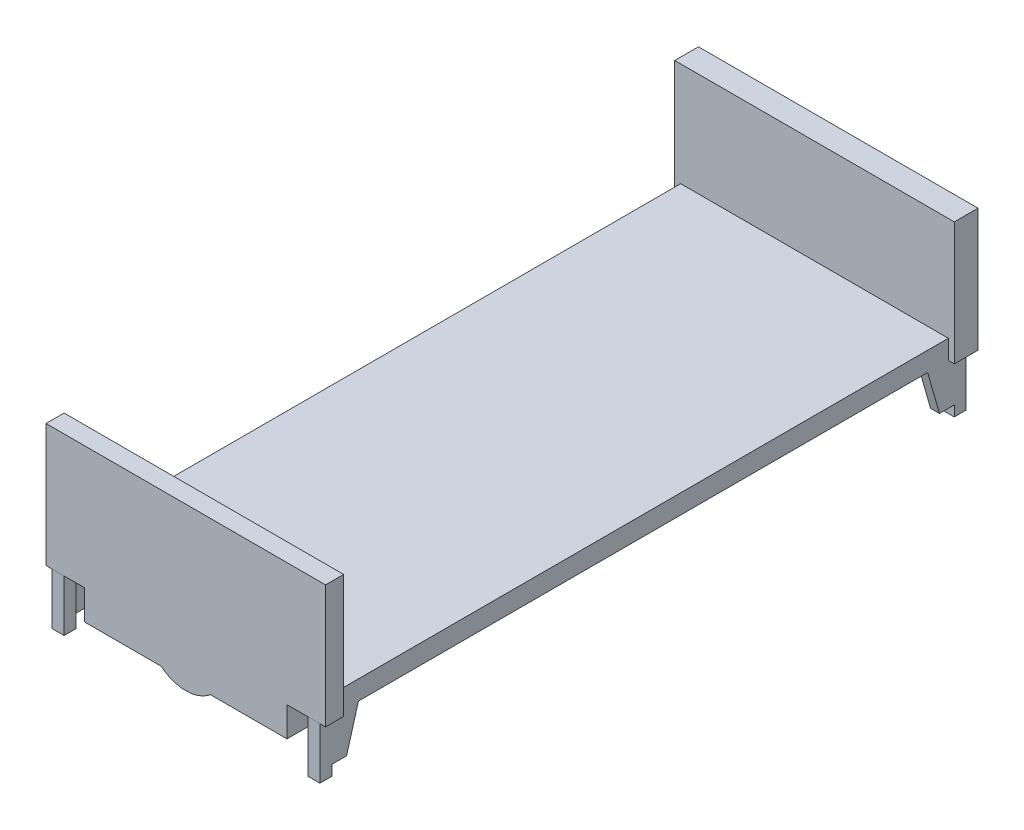
SolidWorks part; units mm, degrees
note: The reader was unsure of these and kept them because the rebuilt part matched: shared geometry of "Sketch1<3>", "Sketch1<4>".
ref_plane "Front Plane" through (0, 0, 0) normal (0, 0, 1) x (1, 0, 0)
ref_plane "Top Plane" through (0, 0, 0) normal (0, 1, 0) x (1, 0, 0)
ref_plane "Right Plane" through (0, 0, 0) normal (1, 0, 0) x (0, 0, -1)
sketch "Sketch1" plane through (0, 0, 0) normal (0, 1, 0) x (1, 0, 0)
  line L0 (-411.5, 40) -> (-451.5, 40)
  line L1 (451.5, 0) -> (-451.5, 0)
  line L2 (451.5, 0) -> (451.5, 2180)
  line L3 (451.5, 2180) -> (-451.5, 2180)
  line L4 (-451.5, 0) -> (-451.5, 2180)
  line L5 (-451.5, 0) -> (451.5, 0)
  line L6 (-451.5, 0) -> (-451.5, 50)
  line L7 (-451.5, 50) -> (451.5, 50)
  line L8 (451.5, 0) -> (451.5, 50)
  line L9 (-451.5, 2180) -> (451.5, 2180)
  line L10 (-451.5, 2180) -> (-451.5, 2130)
  line L11 (-451.5, 2130) -> (451.5, 2130)
  line L12 (451.5, 2180) -> (451.5, 2130)
  line L13 (451.5, 0) -> (411.5, 0)
  line L14 (451.5, 0) -> (451.5, 50)
  line L15 (451.5, 50) -> (411.5, 50)
  line L16 (411.5, 0) -> (411.5, 50)
  line L17 (-451.5, 0) -> (-411.5, 0)
  line L18 (-451.5, 0) -> (-451.5, 50)
  line L19 (-451.5, 50) -> (-411.5, 50)
  line L20 (-411.5, 0) -> (-411.5, 50)
  line L21 (-451.5, 2130) -> (-411.5, 2130)
  line L22 (-451.5, 2130) -> (-451.5, 2180)
  line L23 (-451.5, 2180) -> (-411.5, 2180)
  line L24 (-411.5, 2130) -> (-411.5, 2180)
  line L25 (451.5, 2180) -> (411.5, 2180)
  line L26 (451.5, 2180) -> (451.5, 2130)
  line L27 (451.5, 2130) -> (411.5, 2130)
  line L28 (411.5, 2180) -> (411.5, 2130)
  line L29 (451.5, 40) -> (411.5, 40)
  line L30 (-451.5, 2140) -> (-411.5, 2140)
  line L31 (411.5, 2140) -> (451.5, 2140)
  line L33 (-471.5, 2200) -> (471.5, 2200)
  line L34 (-471.5, 2200) -> (-471.5, 2120)
  line L35 (-471.5, 2120) -> (471.5, 2120)
  line L36 (471.5, 2200) -> (471.5, 2120)
  line L37 (-471.5, 60) -> (471.5, 60)
  line L38 (-471.5, 60) -> (-471.5, -1)
  line L39 (-471.5, -1) -> (471.5, -1)
  line L40 (471.5, 60) -> (471.5, -1)
  dimension "D1" = 2180
  dimension "D2" = 903
  dimension "D3" = 50
  dimension "D4" = 50
  dimension "D5" = 40
  dimension "D6" = 40
  dimension "D7" = 40
  dimension "D8" = 40
  dimension "D9" = 40
  dimension "D10" = 40
  dimension "D11" = 40
  dimension "D12" = 20
  dimension "D13" = 10
  dimension "D14" = 20
  dimension "D15" = 20
  dimension "D16" = 10
  dimension "D17" = 1
  dimension "D18" = 20
  dimension "D19" = 20
extrude "Boss-Extrude1" add sketch "Sketch1" against normal blind 65 contours L4 L37 L2 L35
extrude "Boss-Extrude2" add sketch "Sketch1<3>" against normal blind 50 and the other way blind 350 contours L38 L39 L40 L37 | L33 L36 L35 L34
sketch "Sketch1<3>" plane through (0, 0, 0) normal (0, 1, 0) x (1, 0, 0) same geometry as "Sketch1"
extrude "Boss-Extrude3" add sketch "Sketch1<4>" against normal blind 240 contours L28 L31 L26 L3 | L22 L30 L24 L9 | L1 L20 L0 L4 | L2 L29 L16 L1
sketch "Sketch1<4>" plane through (0, 0, 0) normal (0, 1, 0) x (1, 0, 0) same geometry as "Sketch1"
sketch "Sketch3" plane through (451.5, 0, 0) normal (1, 0, 0) x (0, 0, -1)
  line L0 (60, -65) -> (2120, -65) construction
  line L3 (40, -205) -> (90, -205)
  line L4 (2140, -240) -> (2140, -65) construction
  line L5 (2050, -65) -> (2090, -205)
  line L6 (2090, -205) -> (2140, -205)
  line L7 (90, -205) -> (130, -65)
  line L8 (2140, -240) -> (2140, -65) construction
  line L9 (40, -240) -> (40, -65) construction
  line L10 (40, -205) -> (40, -65)
  line L11 (40, -65) -> (130, -65)
  line L12 (2140, -205) -> (2140, -65)
  line L13 (2140, -65) -> (2050, -65)
  dimension "D1" = 140
  dimension "D2" = 90
  dimension "D3" = 140
  dimension "D4" = 90
  dimension "D5" = 50
  dimension "D6" = 50
extrude "Boss-Extrude4" add sketch "Sketch3" against normal blind 30
sketch "Sketch4" plane through (-451.5, 0, -45.75) normal (1, 0, 0) x (0, 0, -1)
  line L0 (2094.25, -205) -> (2094.25, -65)
  line L2 (2094.25, -240) -> (2094.25, -65) construction
  line L3 (84.25, -65) -> (44.25, -205)
  line L5 (2004.25, -65) -> (2044.25, -205)
  line L6 (2044.25, -205) -> (2094.25, -205)
  line L7 (44.25, -205) -> (-5.75, -205)
  line L8 (2094.25, -65) -> (2004.25, -65)
  line L9 (-5.75, -205) -> (-5.75, -65)
  line L10 (-5.75, -65) -> (84.25, -65)
  line L11 (14.25, -65) -> (2074.25, -65) construction
  line L12 (-5.75, -240) -> (-5.75, -65) construction
  dimension "D1" = 90
  dimension "D2" = 140
  dimension "D3" = 90
  dimension "D4" = 140
  dimension "D5" = 50
  dimension "D6" = 50
extrude "Boss-Extrude5" add sketch "Sketch4" along normal blind 30
sketch "Sketch5" plane through (0, -240, 0) normal (0, -1, 0) x (1, 0, 0)
  line L0 (-431.5, -2180) -> (-431.5, 0)
  line L1 (-416.5, -2175) -> (-446.5, -2175)
  line L2 (-416.5, -2175) -> (-416.5, -2145)
  line L3 (-416.5, -2145) -> (-446.5, -2145)
  line L4 (-446.5, -2175) -> (-446.5, -2145)
  line L5 (416.5, -2175) -> (446.5, -2175)
  line L6 (416.5, -2175) -> (416.5, -2145)
  line L7 (416.5, -2145) -> (446.5, -2145)
  line L8 (446.5, -2175) -> (446.5, -2145)
  line L9 (416.5, -35) -> (446.5, -35)
  line L10 (416.5, -35) -> (416.5, -5)
  line L11 (416.5, -5) -> (446.5, -5)
  line L12 (446.5, -35) -> (446.5, -5)
  line L13 (-446.5, -35) -> (-416.5, -35)
  line L14 (-446.5, -35) -> (-446.5, -5)
  line L15 (-446.5, -5) -> (-416.5, -5)
  line L16 (-416.5, -35) -> (-416.5, -5)
  line L17 (-451.5, -2160) -> (451.5, -2160)
  line L18 (-411.5, 0) -> (-451.5, 0) construction
  line L19 (-451.5, 0) -> (-451.5, -40) construction
  line L20 (451.5, 0) -> (411.5, 0) construction
  line L21 (451.5, 0) -> (451.5, -40) construction
  line L22 (-451.5, -20) -> (451.5, -20)
  line L25 (431.5, 0) -> (431.5, -2180)
  line L27 (451.5, -2180) -> (411.5, -2180) construction
  line L32 (451.5, -2140) -> (451.5, -2180) construction
  line L33 (-451.5, -2140) -> (-451.5, -2180) construction
  line L34 (-411.5, -2180) -> (-451.5, -2180) construction
  point P16 (-446.5, -2160)
  point P29 (-431.5, -5)
  point P36 (-446.5, -20)
  point P43 (431.5, -2175)
  dimension "D1" = 30
extrude "Cut-Extrude1" cut sketch "Sketch5" against normal blind 200 contours L4 L3 L2 L1 | L6 L7 L8 L5 | L10 L11 L12 L9 | L14 L15 L16 L13
sketch "Sketch6" plane through (0, 0, 1) normal (0, 0, 1) x (1, 0, 0)
  line L1 (130, -65) -> (-130, -65)
  line L2 (-471.5, -65) -> (471.5, -65) construction
  arc A0 (-130, -65) -> (130, -65) centre (0, -65) ccw
  dimension "D1" = 130
extrude "Boss-Extrude6" add sketch "Sketch6" against normal blind 30
sketch "Sketch7" plane through (0, 0, -2200) normal (0, 0, -1) x (-1, 0, 0)
  line L1 (130, -65) -> (-130, -65)
  line L2 (471.5, -65) -> (-471.5, -65) construction
  arc A0 (130, -65) -> (-130, -65) centre (0, -65) cw
  dimension "D1" = 130
extrude "Boss-Extrude7" add sketch "Sketch7" against normal blind 30
sketch3d "3DSketch1"
  line L0 (0, -195, -29) -> (0, -165, -29)
  line L1 (0, -165, -29) -> (0, -165, -2170)
  line L2 (0, -165, -2170) -> (0, -195, -2170)
  line L3 (0, -195, -2170) -> (0, -195, -29)
  arc A0 (-130, -65, -29) -> (130, -65, -29) centre (0, -65, -29) ccw construction
  arc A1 (130, -65, -2170) -> (-130, -65, -2170) centre (0, -65, -2170) ccw construction
  point P6 (0, -65, 101)
  point P12 (0, -65, -2300)
  dimension "D1" = 30
extrude "Boss-Extrude8" add sketch "3DSketch1" along a picked direction on the side of the normal blind 15 and the other way blind 15 contours L1 L2 L3 L0
sketch "Sketch8" plane through (0, -65, 0) normal (0, -1, 0) x (1, 0, 0)
  line L0 (130, 1) -> (471.5, 1) construction
  line L1 (-341.5, 1) -> (341.5, 1)
  line L2 (-341.5, 1) -> (-341.5, -419)
  line L3 (-341.5, -419) -> (341.5, -419)
  line L4 (341.5, 1) -> (341.5, -419)
  line L5 (451.5, -130) -> (451.5, -2050) construction
  line L6 (-341.5, -209) -> (-451.5, -209)
  line L7 (-451.5, -130) -> (-451.5, -2050) construction
  line L8 (341.5, -209) -> (451.5, -209)
  dimension "D1" = 110
  dimension "D2" = 420
extrude "Boss-Extrude9" add sketch "Sketch8" along normal blind 100 contours L1 L4 L3 L2
sketch3d "3DSketch2"
  line L0 (471.5, 0, -2200) -> (-471.5, 0, -2200)
  line L1 (471.5, -65, -2200) -> (471.5, 350, -2200) construction
  line L2 (-471.5, -65, -2200) -> (-471.5, 350, -2200) construction
  line L3 (0, 350, -2200) -> (0, 0, -2200)
  line L4 (-471.5, 350, -2200) -> (471.5, 350, -2200) construction
